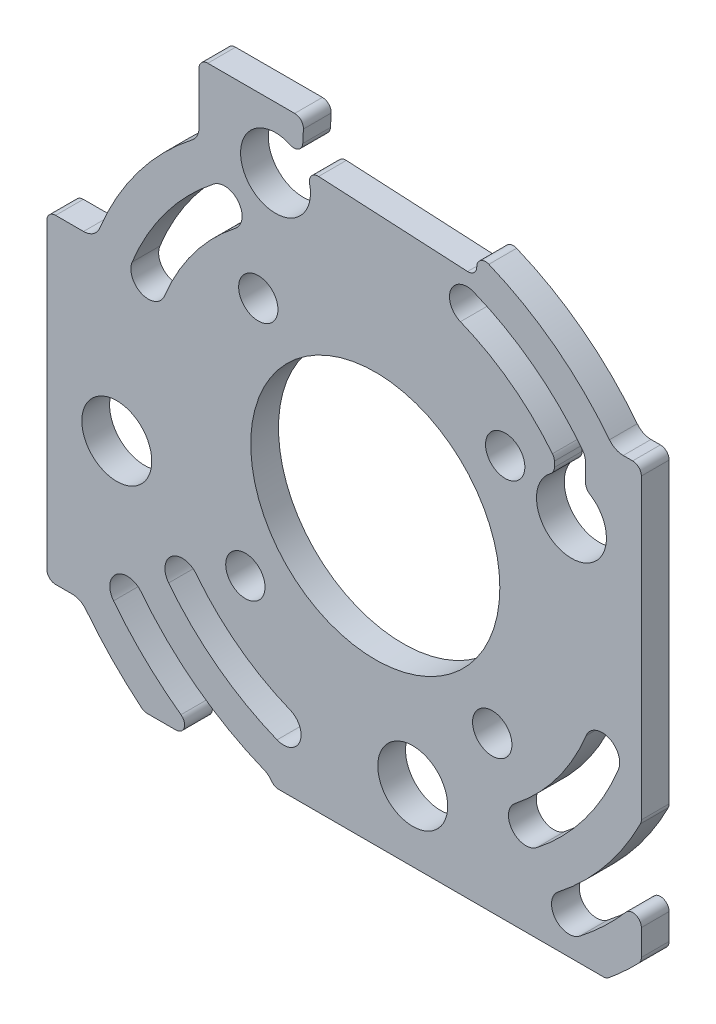
SolidWorks part; units mm, degrees
material "MDF"
ref_plane "Front Plane" through (0, 0, 0) normal (0, 0, 1) x (1, 0, 0)
ref_plane "Top Plane" through (0, 0, 0) normal (0, 1, 0) x (1, 0, 0)
ref_plane "Right Plane" through (0, 0, 0) normal (1, 0, 0) x (0, 0, -1)
sketch "Sketch1" plane through (0, 0, 0) normal (0, 0, 1) x (1, 0, 0)
  line L0 (-6.6325, 45.4094) -> (11.3428, 44.4673) construction
  line L1 (30.4449, -32.63) -> (-37.573, -32.63)
  line L2 (30.4449, -32.63) -> (30.4449, 48.4731)
  line L3 (30.4449, 48.4731) -> (-37.573, 52.0377)
  line L4 (-37.573, -32.63) -> (-37.573, 52.0377)
  circle A0 centre (0, 0) radius 20 construction
  circle A1 centre (0, 0) radius 14.25
  circle A5 centre (-29.573, -7.3783) radius 4
  circle A6 centre (-11.4133, 28.2619) radius 4
  circle A7 centre (22.4449, 11.0103) radius 4
  circle A8 centre (4.2853, -24.63) radius 4
  point P0 (0, 0)
  dimension "D1" = 40
  dimension "D3" = 28.5
  dimension "D4" = 8
  dimension "D6" = 8
  dimension "D7" = 8
  dimension "D5" = 8
  dimension "D2" = 5
extrude "Boss-Extrude1" add sketch "Sketch1" along normal blind 3.175
sketch "Sketch2" plane through (0, 0, 0) normal (0, 0, -1) x (-1, 0, 0)
  line L0 (14.8629, -13.3826) -> (-14.8629, 13.3826) construction
  line L1 (13.3826, 14.8629) -> (-13.3826, -14.8629) construction
  circle A0 centre (0, 0) radius 20 construction
  point P18 (-14.8629, 13.3826)
  point P24 (13.3826, 14.8629)
  point P27 (14.8629, -13.3826)
  point P30 (-13.3826, -14.8629)
hole_wizard "M4 Clearance Hole1" positions "Sketch2" profile "Sketch3" hole size "M4" standard "ANSI Metric" end condition through all
sketch "Sketch3" plane through (14.8629, 13.3826, 0) normal (1, 0, 0) x (0, 1, 0)
  line L0 (0, 0) -> (0, 3.175)
  line L1 (0, 3.175) -> (2.25, 3.175)
  line L2 (2.25, 3.175) -> (2.25, 0)
  line L5 (2.25, 0) -> (0, 0)
  line L11 (0, -6.35) -> (0, 107.95) construction
  dimension "Thru Hole Dia." = 4.5
  dimension "Thru Hole Depth" = 3.175
sketch "Sketch4" plane through (0, 0, 0) normal (0, 0, 1) x (1, 0, 0)
  arc A4 (-23.3951, 29.9444) -> (-35.233, 14.2351) centre (0, 0) ccw
  arc A5 (-35.233, 14.2351) -> (-31.5243, 12.7366) centre (-33.3786, 13.4858) ccw
  arc A6 (-20.9325, 26.7924) -> (-31.5243, 12.7366) centre (0, 0) ccw
  arc A7 (-20.9325, 26.7924) -> (-23.3951, 29.9444) centre (-22.1638, 28.3684) ccw
  arc A8 (-23.3951, 29.9444) -> (-35.233, 14.2351) centre (0, 0) ccw
  arc A9 (-35.233, 14.2351) -> (-31.5243, 12.7366) centre (-33.3786, 13.4858) ccw
  arc A10 (-20.9325, 26.7924) -> (-31.5243, 12.7366) centre (0, 0) ccw
  arc A11 (-20.9325, 26.7924) -> (-23.3951, 29.9444) centre (-22.1638, 28.3684) ccw
  arc A12 (-18.4698, 23.6403) -> (-27.8155, 11.2382) centre (0, 0) ccw
  arc A13 (-27.8155, 11.2382) -> (-24.1068, 9.7398) centre (-25.9611, 10.489) ccw
  arc A14 (-16.0072, 20.4883) -> (-24.1068, 9.7398) centre (0, 0) ccw
  arc A15 (-16.0072, 20.4883) -> (-18.4698, 23.6403) centre (-17.2385, 22.0643) ccw
  arc A16 (-18.4698, 23.6403) -> (-27.8155, 11.2382) centre (0, 0) ccw
  arc A17 (-27.8155, 11.2382) -> (-24.1068, 9.7398) centre (-25.9611, 10.489) ccw
  arc A18 (-16.0072, 20.4883) -> (-24.1068, 9.7398) centre (0, 0) ccw
  arc A19 (-16.0072, 20.4883) -> (-18.4698, 23.6403) centre (-17.2385, 22.0643) ccw
  arc A20 (-42.6505, 17.2319) -> (-38.9417, 15.7335) centre (-40.7961, 16.4827) ccw
  arc A21 (-25.8578, 33.0965) -> (-38.9417, 15.7335) centre (0, 0) ccw
  arc A22 (-25.8578, 33.0965) -> (-28.3204, 36.2485) centre (-27.0891, 34.6725) ccw
  arc A23 (-28.3204, 36.2485) -> (-42.6505, 17.2319) centre (0, 0) ccw
  arc A24 (-42.6505, 17.2319) -> (-38.9417, 15.7335) centre (-40.7961, 16.4827) ccw
  arc A25 (-25.8578, 33.0965) -> (-38.9417, 15.7335) centre (0, 0) ccw
  arc A26 (-25.8578, 33.0965) -> (-28.3204, 36.2485) centre (-27.0891, 34.6725) ccw
  arc A27 (-28.3204, 36.2485) -> (-42.6505, 17.2319) centre (0, 0) ccw
  dimension "D1" = 0
  dimension "D2" = 0
  dimension "D3" = 0
extrude "VentHoles" cut sketch "Sketch4" along normal through all
pattern_circular "CirPattern1" count 4 over 360 about axis through (0, 0, 3.175) along (0, 0, -1) of "VentHoles"
sketch "Sketch5" plane through (0, 0, 0) normal (0, 0, 1) x (1, 0, 0)
  line L1 (12.3414, 44.415) -> (11.5564, 29.4355)
  line L2 (12.2891, 43.4163) -> (11.9202, 36.3769) construction
  line L3 (-7.6835, 44.4631) -> (-8.3639, 31.4809) construction
  line L4 (-6.6325, 45.4094) -> (11.3428, 44.4673) construction
  line L5 (-8.4162, 30.4822) -> (11.5564, 29.4355)
  line L6 (-7.6312, 45.4617) -> (-8.4162, 30.4822)
  line L7 (-7.6312, 45.4617) -> (12.3414, 44.415)
  line L8 (-7.4176, 30.4299) -> (10.5577, 29.4879) construction
  line L10 (-7.4176, 30.4299) -> (10.5577, 29.4879) construction
extrude "Cut-Extrude2" cut sketch "Sketch5" along normal through all
sketch "Sketch7" plane through (0, 0, 0) normal (0, 0, 1) x (1, 0, 0)
  line L0 (-37.573, 52.0377) -> (-37.573, 26.5381) construction
  line L1 (-37.573, 35.2619) -> (30.4449, 35.2619)
  line L2 (-37.573, 35.2619) -> (-37.573, 48.4731)
  line L3 (-37.573, 48.4731) -> (30.4449, 48.4731)
  line L4 (30.4449, 35.2619) -> (30.4449, 48.4731)
  arc A0 (-8.395, 30.8867) -> (-8.0743, 30.4643) centre (-11.4133, 28.2619) ccw construction
  dimension "D1" = 7
extrude "Cut-Extrude3" cut sketch "Sketch7" against normal through all both and the other way through all
delete or keep bodies "Body-Delete/Keep 1" type delete bodies bodies 114 116 118 115
sketch "Sketch9" plane through (0, 0, 3.175) normal (0, 0, 1) x (1, 0, 0)
  line L0 (20.4883, 16.0072) -> (20.4883, 14.4991)
  line L1 (24.0643, 17.2385) -> (24.0643, 14.6678)
  circle A0 centre (22.4449, 11.0103) radius 4 construction
  arc A2 (20.4883, 16.0072) -> (23.6403, 18.4698) centre (22.0643, 17.2385) ccw construction
  circle A3 centre (22.4449, 11.0103) radius 4
  arc A4 (20.4883, 16.0072) -> (23.6403, 18.4698) centre (22.0643, 17.2385) ccw
extrude "Cut-Extrude4" cut sketch "Sketch9" against normal through all both and the other way through all contours A4 L0 A3 L1 region at (22.7301, 15.3049, 3.175)
sketch "Sketch10" plane through (0, 0, 3.175) normal (0, 0, 1) x (1, 0, 0)
  line L0 (-34.6725, -25.0891) -> (-37.573, -25.0891)
  line L1 (-37.573, 18.7689) -> (-37.573, -32.63) construction
  line L2 (28.3684, 20.1638) -> (30.4449, 20.1638)
  line L3 (30.4449, -15.1363) -> (30.4449, 28.9328) construction
  line L4 (-37.573, -25.0891) -> (-37.573, -32.63)
  line L5 (-37.573, -32.63) -> (-30.4501, -32.63)
  line L6 (-30.4501, -32.63) -> (-34.6725, -25.0891)
  line L7 (30.4449, 20.1638) -> (30.4449, 36.986)
  line L8 (30.4449, 36.986) -> (11.7757, 36.986)
  line L9 (11.7757, 36.986) -> (28.3684, 20.1638)
  line L10 (-20.1638, 28.3684) -> (-20.1638, 35.2619)
  line L11 (-25.1779, 35.2619) -> (-8.1657, 35.2619) construction
  line L12 (-33.3786, 11.4858) -> (-37.573, 11.4858)
  line L13 (-25.1779, 35.2619) -> (-8.1657, 35.2619)
  line L14 (-37.573, 18.7689) -> (-37.573, -32.63)
  arc A0 (-33.0965, -25.8578) -> (-36.2485, -28.3204) centre (-34.6725, -27.0891) ccw construction
  arc A1 (26.7924, 20.9325) -> (29.9444, 23.3951) centre (28.3684, 22.1638) ccw construction
  arc A2 (-20.9325, 26.7924) -> (-23.3951, 29.9444) centre (-22.1638, 28.3684) ccw construction
  arc A3 (-35.233, 14.2351) -> (-31.5243, 12.7366) centre (-33.3786, 13.4858) ccw construction
  arc A4 (-25.8578, 33.0965) -> (-25.1779, 35.2619) centre (-27.0891, 34.6725) ccw construction
  arc A5 (-25.8578, 33.0965) -> (-37.573, 18.7689) centre (0, 0) ccw construction
  arc A6 (-25.8578, 33.0965) -> (-25.1779, 35.2619) centre (-27.0891, 34.6725) ccw
  arc A7 (-25.8578, 33.0965) -> (-37.573, 18.7689) centre (0, 0) ccw
  arc A8 (-23.3951, 29.9444) -> (-35.233, 14.2351) centre (0, 0) ccw construction
  arc A9 (-20.9325, 26.7924) -> (-23.3951, 29.9444) centre (-22.1638, 28.3684) ccw
  arc A10 (-35.233, 14.2351) -> (-31.5243, 12.7366) centre (-33.3786, 13.4858) ccw
  arc A11 (-23.3951, 29.9444) -> (-35.233, 14.2351) centre (0, 0) ccw
extrude "Cut-Extrude5" cut sketch "Sketch10" against normal through all both and the other way through all contours L5 L6 L0 L4 | L8 L9 L2 L7 | A11 A9 L10 L13 A6 A7 L14 L12 A10 region at (-34.9189, -29.389, 3.175) region at (-29.8319, 25.1655, 3.175) region at (24.1526, 30.8173, 3.175)
fillet "Fillet1" radius 1 19 edges at (30.4449, -28.9328, 1.5875) (26.444, -32.63, 1.5875) (-11.6312, -32.63, 1.5875) (-19.4752, -32.63, 1.5875) (11.7144, 32.4502, 1.5875) (-8.1657, 35.2619, 1.5875) (-26.444, -32.63, 1.5875) (11.5564, 29.4355, 1.5875) (-8.395, 30.8867, 1.5875) (-8.0743, 30.4643, 1.5875) (20.4883, 16.0072, 1.5875) (20.4883, 14.4991, 1.5875) (24.0643, 14.6678, 1.5875) (30.4449, -22.74, 1.5875) (-37.573, -25.0891, 1.5875) (30.4449, -15.1363, 1.5875) (30.4449, 20.1638, 1.5875) (-20.1638, 35.2619, 1.5875) (-37.573, 11.4858, 1.5875)
